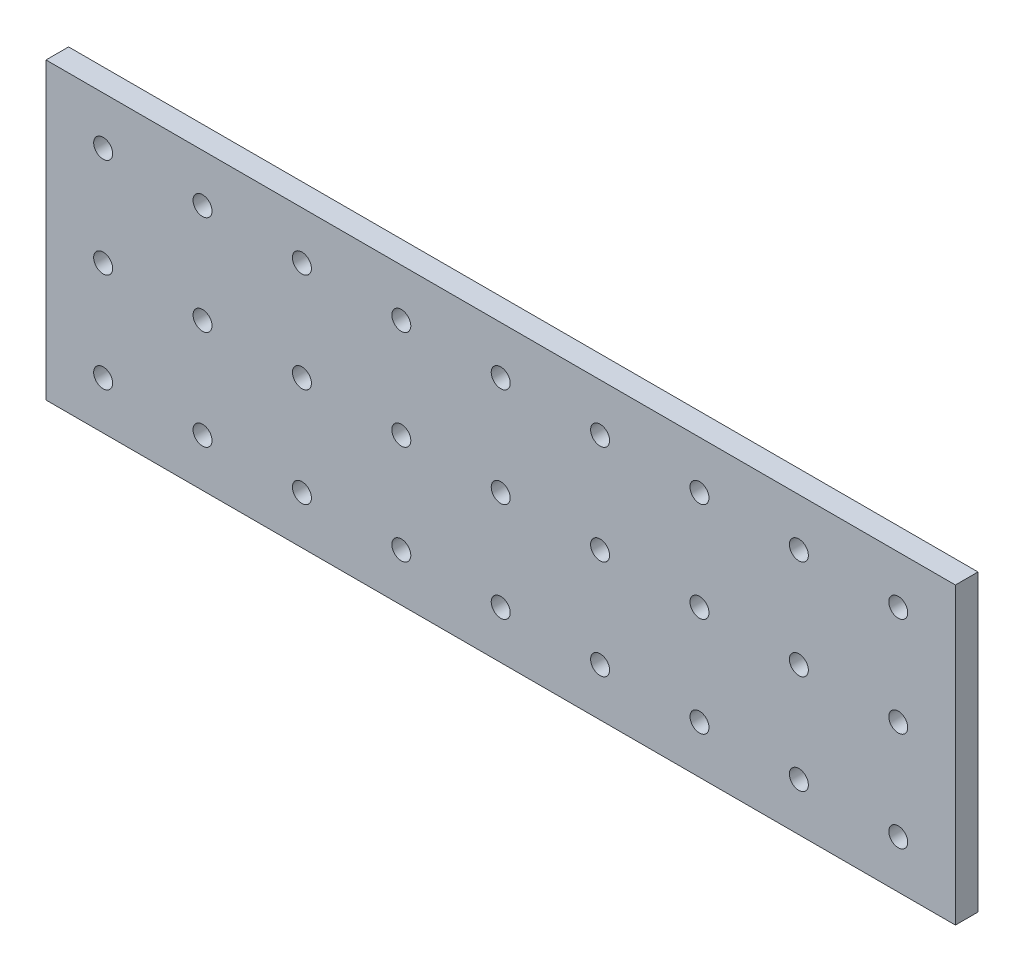
SolidWorks part; units mm, degrees
ref_plane "Plano frontal" through (0, 0, 0) normal (0, 0, 1) x (1, 0, 0)
ref_plane "Plano superior" through (0, 0, 0) normal (0, 1, 0) x (1, 0, 0)
ref_plane "Plano direito" through (0, 0, 0) normal (1, 0, 0) x (0, 0, -1)
sketch "Esboço1" plane through (0, 0, 0) normal (0, 0, 1) x (1, 0, 0)
  line L1 (0, 0) -> (201.3, 0)
  line L2 (0, 0) -> (0, 65.2)
  line L3 (0, 65.2) -> (201.3, 65.2)
  line L4 (201.3, 0) -> (201.3, 65.2)
  dimension "D1" = 201.3
  dimension "65.2" = 65.2
extrude "Ressalto-extrusão1" add sketch "Esboço1" along normal blind 5
sketch "Esboço2" plane through (0, 0, 0) normal (0, 0, 1) x (1, 0, 0)
  line L0 (0, 32.6) -> (201.3, 32.6) construction
  line L1 (0, 65.2) -> (0, 0) construction
  line L2 (201.3, 0) -> (201.3, 65.2) construction
  line L3 (201.3, 32.6) -> (100.65, 65.2) construction
  line L4 (201.3, 65.2) -> (0, 65.2) construction
  line L5 (100.65, 65.2) -> (100.65, 0) construction
  line L6 (0, 0) -> (201.3, 0) construction
  line L7 (100.65, 87.2) -> (100.65, 22) construction
  line L8 (100.65, 32.6) -> (100.65, 54.6) construction
  line L9 (100.65, 43.2) -> (100.65, -22) construction
  line L10 (100.65, 32.6) -> (100.65, 10.6) construction
  line L11 (122.65, 32.6) -> (122.65, 54.6) construction
  line L12 (122.65, 32.6) -> (122.65, 10.6) construction
  line L13 (144.65, 32.6) -> (144.65, 54.6) construction
  line L14 (144.65, 32.6) -> (144.65, 10.6) construction
  line L15 (166.65, 32.6) -> (166.65, 54.6) construction
  line L16 (166.65, 32.6) -> (166.65, 10.6) construction
  line L17 (188.65, 32.6) -> (188.65, 54.6) construction
  line L18 (188.65, 32.6) -> (188.65, 10.6) construction
  line L19 (100.65, 32.6) -> (122.65, 32.6) construction
  line L20 (78.65, 32.6) -> (78.65, 54.6) construction
  line L21 (78.65, 32.6) -> (78.65, 10.6) construction
  line L22 (56.65, 32.6) -> (56.65, 54.6) construction
  line L23 (56.65, 32.6) -> (56.65, 10.6) construction
  line L24 (34.65, 32.6) -> (34.65, 54.6) construction
  line L25 (34.65, 32.6) -> (34.65, 10.6) construction
  line L26 (12.65, 32.6) -> (12.65, 54.6) construction
  line L27 (12.65, 32.6) -> (12.65, 10.6) construction
  line L28 (100.65, 32.6) -> (78.65, 32.6) construction
  circle A0 centre (100.65, 32.6) radius 2.1
  circle A1 centre (100.65, 54.6) radius 2.1
  circle A2 centre (100.65, 10.6) radius 2.1
  circle A3 centre (122.65, 32.6) radius 2.1
  circle A4 centre (122.65, 54.6) radius 2.1
  circle A5 centre (122.65, 10.6) radius 2.1
  circle A6 centre (144.65, 32.6) radius 2.1
  circle A7 centre (144.65, 54.6) radius 2.1
  circle A8 centre (144.65, 10.6) radius 2.1
  circle A9 centre (166.65, 32.6) radius 2.1
  circle A10 centre (166.65, 54.6) radius 2.1
  circle A11 centre (166.65, 10.6) radius 2.1
  circle A12 centre (188.65, 32.6) radius 2.1
  circle A13 centre (188.65, 54.6) radius 2.1
  circle A14 centre (188.65, 10.6) radius 2.1
  circle A15 centre (78.65, 32.6) radius 2.1
  circle A16 centre (78.65, 54.6) radius 2.1
  circle A17 centre (78.65, 10.6) radius 2.1
  circle A18 centre (56.65, 32.6) radius 2.1
  circle A19 centre (56.65, 54.6) radius 2.1
  circle A20 centre (56.65, 10.6) radius 2.1
  circle A21 centre (34.65, 32.6) radius 2.1
  circle A22 centre (34.65, 54.6) radius 2.1
  circle A23 centre (34.65, 10.6) radius 2.1
  circle A24 centre (12.65, 32.6) radius 2.1
  circle A25 centre (12.65, 54.6) radius 2.1
  circle A26 centre (12.65, 10.6) radius 2.1
  dimension "D1" = 4.2
  dimension "D2" = 22
  dimension "D3" = 22
  dimension "D6" = 22
  dimension "D7" = 22
  dimension "D5" = 2
  dimension "D4" = 2
extrude "Corte-extrusão1" cut sketch "Esboço2" along direction (0, 0, -1) on the side of the normal blind 30
